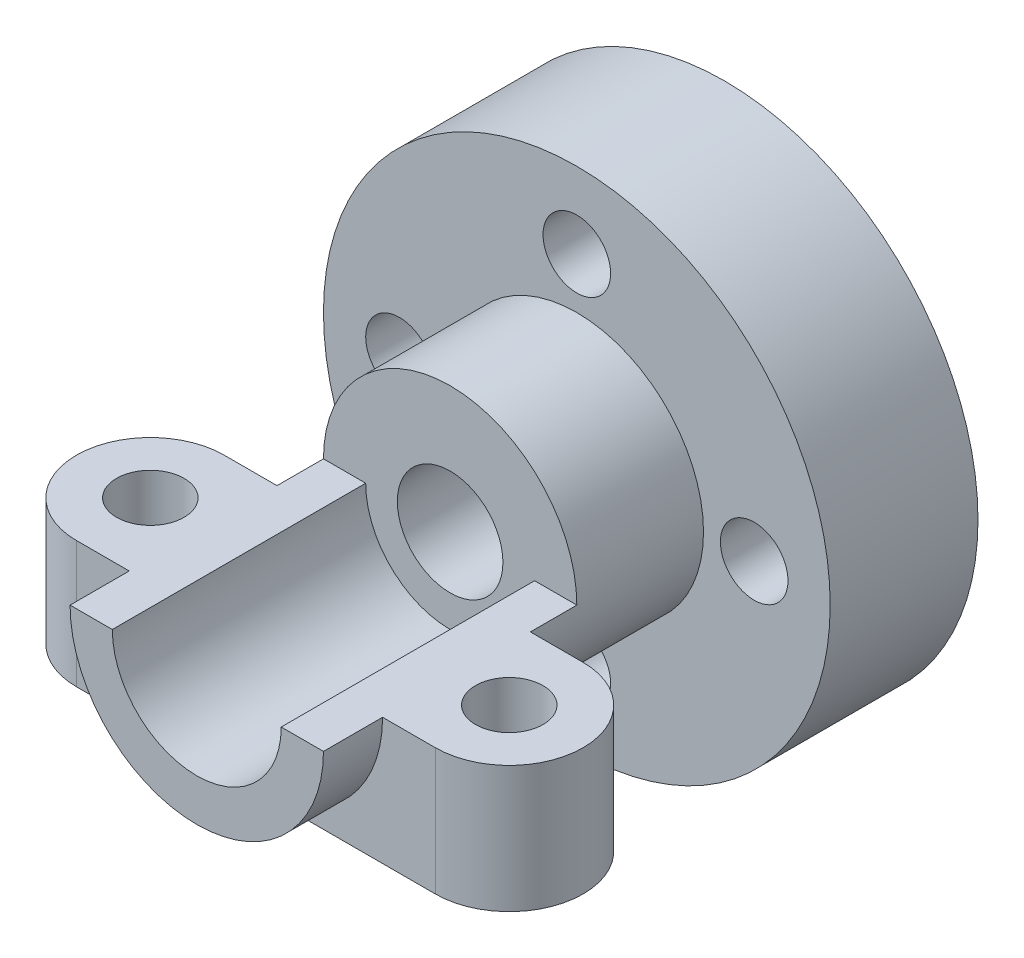
SolidWorks part; units mm, degrees
ref_plane "Front Plane" through (0, 0, 0) normal (0, 0, 1) x (1, 0, 0)
ref_plane "Top Plane" through (0, 0, 0) normal (0, 1, 0) x (1, 0, 0)
ref_plane "Right Plane" through (0, 0, 0) normal (1, 0, 0) x (0, 0, -1)
sketch "Sketch1" plane through (0, 0, 0) normal (0, 0, 1) x (1, 0, 0)
  line L0 (0, 0) -> (0, 41667.8352) construction
  line L1 (0, 0) -> (-41667.8352, 0) construction
  line L2 (20, 0) -> (30, 0)
  line L3 (-20, 0) -> (-30, 0)
  circle A0 centre (0, 0) radius 30
  circle A2 centre (0, 0) radius 12.5
  circle A3 centre (0, 0) radius 42 construction
  circle A4 centre (0, 0) radius 60
  circle A5 centre (42, 0) radius 8
  circle A6 centre (0, 0) radius 60
  circle A7 centre (0, -42) radius 8
  circle A8 centre (0, 0) radius 60
  circle A9 centre (-42, 0) radius 8
  circle A10 centre (0, 0) radius 60
  circle A11 centre (0, 42) radius 8
  arc A12 (-20, 0) -> (20, 0) centre (0, 0) ccw
  point P27 (0, 0)
  dimension "D1" = 25
  dimension "D2" = 60
  dimension "D3" = 84
  dimension "D4" = 120
  dimension "D5" = 16
  dimension "D7" = 20
  dimension "D6" = 4
extrude "Boss-Extrude1" add sketch "Sketch1" along normal blind 125 contours A12 L3 A0 L2 region at (25, -0.6708, 0)
extrude "Boss-Extrude2" add sketch "Sketch1<4>" along normal blind 65 contours L3 A12 L2 A0 A2 region at (0, -19.219, 0)
sketch "Sketch1<4>" plane through (0, 0, 0) normal (0, 0, 1) x (1, 0, 0) same geometry as "Sketch1"
extrude "Boss-Extrude3" add sketch "Sketch1<5>" along normal blind 35 contours A4 A11 A9 A7 A5 A0 region at (-58.3029, 0, 0)
sketch "Sketch1<5>" plane through (0, 0, 0) normal (0, 0, 1) x (1, 0, 0) same geometry as "Sketch1"
sketch "Sketch2" plane through (0, 0, 125) normal (0, 0, 1) x (1, 0, 0)
  line L0 (30, 0) -> (60, 0)
  line L1 (60, 0) -> (60, -26.3648)
  line L2 (0, -30) -> (60, -30)
  line L3 (60, -30) -> (60, -26.3648)
  line L6 (-20, 0) -> (-30, 0)
  line L7 (30, 0) -> (20, 0)
  arc A2 (-30, 0) -> (30, 0) centre (0, 0) ccw construction
  arc A5 (-20, 0) -> (20, 0) centre (0, 0) ccw
  arc A6 (-30, 0) -> (30, 0) centre (0, 0) ccw
  arc A8 (0, -30) -> (30, 0) centre (0, 0) ccw
  dimension "D1" = 30
  dimension "D2" = 0
extrude "Boss-Extrude4" add sketch "Sketch2" against normal blind 35 from offset 14 offset against normal yes
fillet "Fillet1" 2 edges at (60, -15, 111) (60, -15, 76) type full round first side face at (39.0533, -16.5533, 111) second side face at (39.0533, -16.5533, 76) middle face at (60, -15, 93.5)
hole_wizard "Ø16.0 (16) Diameter Hole1" positions "3DSketch2" profile "Sketch4" hole size "Ø16.0" standard "ANSI Metric" end condition up to next
sketch3d "3DSketch2"
  line L0 (42.5, -30, 93.5) -> (42.5, 0, 93.5) construction
  point P0 (42.5, 0, 93.5)
sketch "Sketch4" plane through (42.5, 0, 93.5) normal (1, 0, 0) x (0, 0, 1)
  line L0 (0, 0) -> (0, 30.001)
  line L1 (0, 30.001) -> (8, 30.001)
  line L2 (8, 30.001) -> (8, 0)
  line L5 (8, 0) -> (0, 0)
  line L11 (0, -6.35) -> (0, 107.95) construction
  dimension "Thru Hole Dia." = 16
  dimension "Thru Hole Depth" = 30.001
mirror "Mirror1" about plane through (0, 0, 0) normal (1, 0, 0) of "Boss-Extrude4", "Fillet1", "Ø16.0 (16) Diameter Hole1"
sketch "Sketch5" plane through (0, 0, 0) normal (0, 0, -1) x (-1, 0, 0)
  circle A0 centre (0, 0) radius 53.7904
extrude "Cut-Extrude2" cut sketch "Sketch5" against normal blind 10
